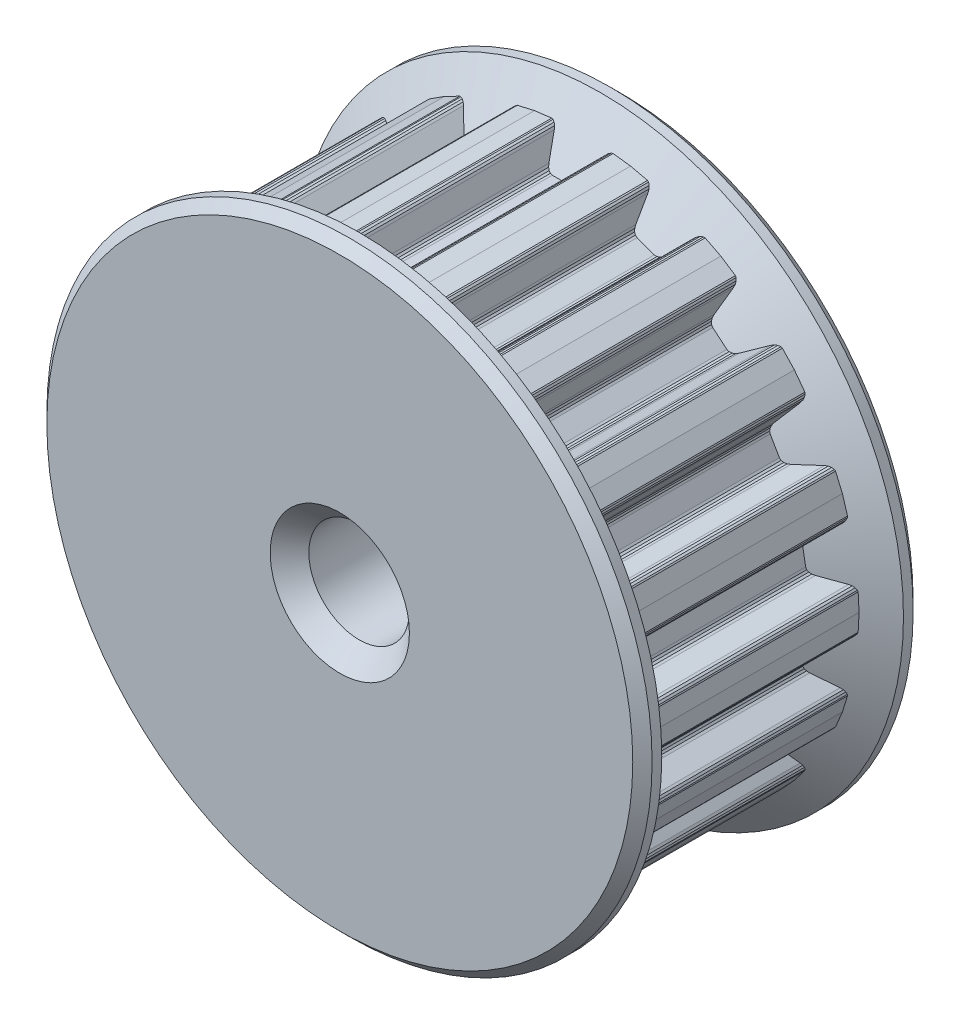
SolidWorks part; units mm, degrees
material "PLA"
ref_plane "Front Plane" through (0, 0, 0) normal (0, 0, 1) x (1, 0, 0)
ref_plane "Top Plane" through (0, 0, 0) normal (0, 1, 0) x (1, 0, 0)
ref_plane "Right Plane" through (0, 0, 0) normal (1, 0, 0) x (0, 0, -1)
sketch "Sketch1" plane through (0, 0, 0) normal (0, 0, 1) x (1, 0, 0)
  circle A0 centre (0, 0) radius 2.6
  circle A1 centre (0, 0) radius 12.65
  dimension "D1" = 5.2
  dimension "D2" = 25.3
extrude "Boss-Extrude1" add sketch "Sketch1" along normal mid plane 12.5
sketch "Sketch2" plane through (0, 0, 6.25) normal (0, 0, 1) x (1, 0, 0)
  circle A5 centre (0, 0) radius 2.6 construction
  circle A6 centre (0, 0) radius 2.6
  circle A8 centre (0, 0) radius 15.65
  circle A9 centre (0, 0) radius 15.65
  dimension "D1" = 3
extrude "Boss-Extrude2" add sketch "Sketch2" along normal blind 1
mirror "Mirror1" about plane through (0, 0, 0) normal (0, 0, 1) of "Boss-Extrude2"
chamfer "Chamfer1" distance 3 angle 35 2 edges at (12.65, 0, 6.25) (12.65, 0, -6.25) first distance on face at (12.65, 0, 6.25) first distance on face at (12.65, 0, -6.25)
chamfer "Chamfer2" distance 0.5 angle 45 2 edges at (15.65, 0, 7.25) (15.65, 0, -7.25)
chamfer "Chamfer3" distance 1 angle 45 2 edges at (2.6, 0, -7.25) (2.6, 0, 7.25)
sketch "Sketch3" plane through (0, 0, 0) normal (0, 0, 1) x (1, 0, 0)
  line L0 (-1.5107, -14.1885) -> (-1.4073, -14.1374)
  line L1 (-1.4073, -14.1374) -> (-1.3209, -14.0571)
  line L2 (-1.3209, -14.0571) -> (-1.2574, -13.9516)
  line L3 (-1.2574, -13.9516) -> (-0.845, -12.9908)
  line L4 (-0.845, -12.9908) -> (-0.7816, -12.8857)
  line L5 (-0.7816, -12.8857) -> (-0.6953, -12.8054)
  line L6 (-0.6953, -12.8054) -> (-0.5918, -12.7541)
  line L7 (-0.5918, -12.7541) -> (-0.477, -12.736)
  line L8 (-0.477, -12.736) -> (0.477, -12.736)
  line L9 (0.477, -12.736) -> (0.5918, -12.7541)
  line L10 (0.5918, -12.7541) -> (0.6953, -12.8054)
  line L11 (0.6953, -12.8054) -> (0.7816, -12.8857)
  line L12 (0.7816, -12.8857) -> (0.845, -12.9908)
  line L13 (0.845, -12.9908) -> (1.2574, -13.9516)
  line L14 (1.2574, -13.9516) -> (1.321, -14.0571)
  line L15 (1.321, -14.0571) -> (1.4074, -14.1374)
  line L16 (1.4074, -14.1374) -> (1.5109, -14.1885)
  line L17 (1.5109, -14.1885) -> (1.585, -14.2001)
  line L18 (1.585, -14.2001) -> (2.483, -14.0819)
  line L19 (2.483, -14.0819) -> (3.3673, -13.8858)
  line L20 (3.3673, -13.8858) -> (3.4332, -13.8495)
  line L21 (3.4332, -13.8495) -> (3.5129, -13.7661)
  line L22 (3.5129, -13.7661) -> (3.5665, -13.6611)
  line L23 (3.5665, -13.6611) -> (3.5902, -13.5403)
  line L24 (3.5902, -13.5403) -> (3.6491, -12.4964)
  line L25 (3.6491, -12.4964) -> (3.6727, -12.376)
  line L26 (3.6727, -12.376) -> (3.7264, -12.2709)
  line L27 (3.7264, -12.2709) -> (3.8061, -12.1873)
  line L28 (3.8061, -12.1873) -> (3.9077, -12.1311)
  line L29 (3.9077, -12.1311) -> (4.8042, -11.8048)
  line L30 (4.8042, -11.8048) -> (4.9182, -11.7825)
  line L31 (4.9182, -11.7825) -> (5.033, -11.7953)
  line L32 (5.033, -11.7953) -> (5.1417, -11.8413)
  line L33 (5.1417, -11.8413) -> (5.2372, -11.9184)
  line L34 (5.2372, -11.9184) -> (5.9533, -12.6802)
  line L35 (5.9533, -12.6802) -> (6.0491, -12.7575)
  line L36 (6.0491, -12.7575) -> (6.1578, -12.8034)
  line L37 (6.1578, -12.8034) -> (6.2725, -12.8161)
  line L38 (6.2725, -12.8161) -> (6.3461, -12.8016)
  line L39 (6.3461, -12.8016) -> (7.1496, -12.3834)
  line L40 (7.1496, -12.3834) -> (7.9135, -11.8967)
  line L41 (7.9135, -11.8967) -> (7.9629, -11.8401)
  line L42 (7.9629, -11.8401) -> (8.0093, -11.7344)
  line L43 (8.0093, -11.7344) -> (8.0238, -11.6174)
  line L44 (8.0238, -11.6174) -> (8.0047, -11.4958)
  line L45 (8.0047, -11.4958) -> (7.703, -10.4947)
  line L46 (7.703, -10.4947) -> (7.684, -10.3735)
  line L47 (7.684, -10.3735) -> (7.6985, -10.2564)
  line L48 (7.6985, -10.2564) -> (7.7448, -10.1506)
  line L49 (7.7448, -10.1506) -> (7.8212, -10.063)
  line L50 (7.8212, -10.063) -> (8.552, -9.4497)
  line L51 (8.552, -9.4497) -> (8.6515, -9.3898)
  line L52 (8.6515, -9.3898) -> (8.7637, -9.3626)
  line L53 (8.7637, -9.3626) -> (8.8816, -9.3686)
  line L54 (8.8816, -9.3686) -> (8.9977, -9.4084)
  line L55 (8.9977, -9.4084) -> (9.9312, -9.8793)
  line L56 (9.9312, -9.8793) -> (10.0476, -9.9192)
  line L57 (10.0476, -9.9192) -> (10.1655, -9.9252)
  line L58 (10.1655, -9.9252) -> (10.2776, -9.8979)
  line L59 (10.2776, -9.8979) -> (10.3418, -9.8591)
  line L60 (10.3418, -9.8591) -> (10.9538, -9.1913)
  line L61 (10.9538, -9.1913) -> (11.5052, -8.4727)
  line L62 (11.5052, -8.4727) -> (11.5323, -8.4025)
  line L63 (11.5323, -8.4025) -> (11.5397, -8.2874)
  line L64 (11.5397, -8.2874) -> (11.5133, -8.1725)
  line L65 (11.5133, -8.1725) -> (11.4538, -8.0647)
  line L66 (11.4538, -8.0647) -> (10.8279, -7.2272)
  line L67 (10.8279, -7.2272) -> (10.7685, -7.1198)
  line L68 (10.7685, -7.1198) -> (10.7422, -7.0048)
  line L69 (10.7422, -7.0048) -> (10.7495, -6.8895)
  line L70 (10.7495, -6.8895) -> (10.7912, -6.7811)
  line L71 (10.7912, -6.7811) -> (11.2682, -5.9549)
  line L72 (11.2682, -5.9549) -> (11.3412, -5.8646)
  line L73 (11.3412, -5.8646) -> (11.4374, -5.8006)
  line L74 (11.4374, -5.8006) -> (11.5502, -5.7659)
  line L75 (11.5502, -5.7659) -> (11.6729, -5.7636)
  line L76 (11.6729, -5.7636) -> (12.7112, -5.8869)
  line L77 (12.7112, -5.8869) -> (12.8343, -5.8845)
  line L78 (12.8343, -5.8845) -> (12.947, -5.8498)
  line L79 (12.947, -5.8498) -> (13.043, -5.7858)
  line L80 (13.043, -5.7858) -> (13.0902, -5.7274)
  line L81 (13.0902, -5.7274) -> (13.4368, -4.8906)
  line L82 (13.4368, -4.8906) -> (13.7092, -4.0267)
  line L83 (13.7092, -4.0267) -> (13.7106, -3.9515)
  line L84 (13.7106, -3.9515) -> (13.6782, -3.8408)
  line L85 (13.6782, -3.8408) -> (13.6142, -3.7418)
  line L86 (13.6142, -3.7418) -> (13.5213, -3.661)
  line L87 (13.5213, -3.661) -> (12.6467, -3.088)
  line L88 (12.6467, -3.088) -> (12.5542, -3.0074)
  line L89 (12.5542, -3.0074) -> (12.4901, -2.9083)
  line L90 (12.4901, -2.9083) -> (12.4576, -2.7975)
  line L91 (12.4576, -2.7975) -> (12.4597, -2.6814)
  line L92 (12.4597, -2.6814) -> (12.6254, -1.7418)
  line L93 (12.6254, -1.7418) -> (12.6631, -1.6319)
  line L94 (12.6631, -1.6319) -> (12.7316, -1.5389)
  line L95 (12.7316, -1.5389) -> (12.8257, -1.4678)
  line L96 (12.8257, -1.4678) -> (12.9402, -1.4237)
  line L97 (12.9402, -1.4237) -> (13.958, -1.1844)
  line L98 (13.958, -1.1844) -> (14.0729, -1.1401)
  line L99 (14.0729, -1.1401) -> (14.167, -1.0689)
  line L100 (14.167, -1.0689) -> (14.2353, -0.9759)
  line L101 (14.2353, -0.9759) -> (14.2596, -0.9049)
  line L102 (14.2596, -0.9049) -> (14.2991, 0)
  line L103 (14.2991, 0) -> (14.2596, 0.9049)
  line L104 (14.2596, 0.9049) -> (14.2353, 0.9761)
  line L105 (14.2353, 0.9761) -> (14.167, 1.069)
  line L106 (14.167, 1.069) -> (14.0729, 1.1401)
  line L107 (14.0729, 1.1401) -> (13.958, 1.1844)
  line L108 (13.958, 1.1844) -> (12.9402, 1.4237)
  line L109 (12.9402, 1.4237) -> (12.8257, 1.4678)
  line L110 (12.8257, 1.4678) -> (12.7316, 1.5389)
  line L111 (12.7316, 1.5389) -> (12.6631, 1.6319)
  line L112 (12.6631, 1.6319) -> (12.6254, 1.7418)
  line L113 (12.6254, 1.7418) -> (12.4597, 2.6814)
  line L114 (12.4597, 2.6814) -> (12.4576, 2.7975)
  line L115 (12.4576, 2.7975) -> (12.4901, 2.9083)
  line L116 (12.4901, 2.9083) -> (12.5542, 3.0074)
  line L117 (12.5542, 3.0074) -> (12.6467, 3.088)
  line L118 (12.6467, 3.088) -> (13.5213, 3.661)
  line L119 (13.5213, 3.661) -> (13.6141, 3.7419)
  line L120 (13.6141, 3.7419) -> (13.6782, 3.841)
  line L121 (13.6782, 3.841) -> (13.7106, 3.9517)
  line L122 (13.7106, 3.9517) -> (13.7091, 4.0267)
  line L123 (13.7091, 4.0267) -> (13.4368, 4.8906)
  line L124 (13.4368, 4.8906) -> (13.0901, 5.7274)
  line L125 (13.0901, 5.7274) -> (13.043, 5.7859)
  line L126 (13.043, 5.7859) -> (12.947, 5.8499)
  line L127 (12.947, 5.8499) -> (12.8342, 5.8846)
  line L128 (12.8342, 5.8846) -> (12.7112, 5.8869)
  line L129 (12.7112, 5.8869) -> (11.6729, 5.7636)
  line L130 (11.6729, 5.7636) -> (11.5502, 5.7659)
  line L131 (11.5502, 5.7659) -> (11.4374, 5.8006)
  line L132 (11.4374, 5.8006) -> (11.3412, 5.8646)
  line L133 (11.3412, 5.8646) -> (11.2682, 5.9549)
  line L134 (11.2682, 5.9549) -> (10.7912, 6.7811)
  line L135 (10.7912, 6.7811) -> (10.7495, 6.8895)
  line L136 (10.7495, 6.8895) -> (10.7422, 7.0048)
  line L137 (10.7422, 7.0048) -> (10.7685, 7.1198)
  line L138 (10.7685, 7.1198) -> (10.8279, 7.2272)
  line L139 (10.8279, 7.2272) -> (11.4538, 8.0647)
  line L140 (11.4538, 8.0647) -> (11.5133, 8.1725)
  line L141 (11.5133, 8.1725) -> (11.5396, 8.2875)
  line L142 (11.5396, 8.2875) -> (11.5322, 8.4027)
  line L143 (11.5322, 8.4027) -> (11.5051, 8.4727)
  line L144 (11.5051, 8.4727) -> (10.9538, 9.1913)
  line L145 (10.9538, 9.1913) -> (10.3418, 9.8591)
  line L146 (10.3418, 9.8591) -> (10.2775, 9.898)
  line L147 (10.2775, 9.898) -> (10.1654, 9.9253)
  line L148 (10.1654, 9.9253) -> (10.0476, 9.9193)
  line L149 (10.0476, 9.9193) -> (9.9312, 9.8793)
  line L150 (9.9312, 9.8793) -> (8.9977, 9.4084)
  line L151 (8.9977, 9.4084) -> (8.8816, 9.3686)
  line L152 (8.8816, 9.3686) -> (8.7637, 9.3626)
  line L153 (8.7637, 9.3626) -> (8.6515, 9.3898)
  line L154 (8.6515, 9.3898) -> (8.552, 9.4497)
  line L155 (8.552, 9.4497) -> (7.8212, 10.063)
  line L156 (7.8212, 10.063) -> (7.7448, 10.1506)
  line L157 (7.7448, 10.1506) -> (7.6985, 10.2564)
  line L158 (7.6985, 10.2564) -> (7.684, 10.3735)
  line L159 (7.684, 10.3735) -> (7.703, 10.4947)
  line L160 (7.703, 10.4947) -> (8.0047, 11.4958)
  line L161 (8.0047, 11.4958) -> (8.0238, 11.6174)
  line L162 (8.0238, 11.6174) -> (8.0092, 11.7345)
  line L163 (8.0092, 11.7345) -> (7.9628, 11.8402)
  line L164 (7.9628, 11.8402) -> (7.9135, 11.8967)
  line L165 (7.9135, 11.8967) -> (7.1496, 12.3834)
  line L166 (7.1496, 12.3834) -> (6.3461, 12.8016)
  line L167 (6.3461, 12.8016) -> (6.2723, 12.8161)
  line L168 (6.2723, 12.8161) -> (6.1577, 12.8035)
  line L169 (6.1577, 12.8035) -> (6.0491, 12.7576)
  line L170 (6.0491, 12.7576) -> (5.9533, 12.6802)
  line L171 (5.9533, 12.6802) -> (5.2372, 11.9184)
  line L172 (5.2372, 11.9184) -> (5.1417, 11.8413)
  line L173 (5.1417, 11.8413) -> (5.033, 11.7953)
  line L174 (5.033, 11.7953) -> (4.9182, 11.7825)
  line L175 (4.9182, 11.7825) -> (4.8042, 11.8048)
  line L176 (4.8042, 11.8048) -> (3.9077, 12.1311)
  line L177 (3.9077, 12.1311) -> (3.8061, 12.1873)
  line L178 (3.8061, 12.1873) -> (3.7264, 12.2709)
  line L179 (3.7264, 12.2709) -> (3.6727, 12.376)
  line L180 (3.6727, 12.376) -> (3.6491, 12.4964)
  line L181 (3.6491, 12.4964) -> (3.5902, 13.5403)
  line L182 (3.5902, 13.5403) -> (3.5665, 13.6611)
  line L183 (3.5665, 13.6611) -> (3.5127, 13.7661)
  line L184 (3.5127, 13.7661) -> (3.433, 13.8496)
  line L185 (3.433, 13.8496) -> (3.3673, 13.8858)
  line L186 (3.3673, 13.8858) -> (2.483, 14.0819)
  line L187 (2.483, 14.0819) -> (1.585, 14.2001)
  line L188 (1.585, 14.2001) -> (1.5107, 14.1885)
  line L189 (1.5107, 14.1885) -> (1.4073, 14.1374)
  line L190 (1.4073, 14.1374) -> (1.3209, 14.0571)
  line L191 (1.3209, 14.0571) -> (1.2574, 13.9516)
  line L192 (1.2574, 13.9516) -> (0.845, 12.9908)
  line L193 (0.845, 12.9908) -> (0.7816, 12.8857)
  line L194 (0.7816, 12.8857) -> (0.6953, 12.8054)
  line L195 (0.6953, 12.8054) -> (0.5918, 12.7541)
  line L196 (0.5918, 12.7541) -> (0.477, 12.736)
  line L197 (0.477, 12.736) -> (-0.477, 12.736)
  line L198 (-0.477, 12.736) -> (-0.5918, 12.7541)
  line L199 (-0.5918, 12.7541) -> (-0.6953, 12.8054)
  line L200 (-0.6953, 12.8054) -> (-0.7816, 12.8857)
  line L201 (-0.7816, 12.8857) -> (-0.845, 12.9908)
  line L202 (-0.845, 12.9908) -> (-1.2574, 13.9516)
  line L203 (-1.2574, 13.9516) -> (-1.321, 14.0571)
  line L204 (-1.321, 14.0571) -> (-1.4074, 14.1374)
  line L205 (-1.4074, 14.1374) -> (-1.5109, 14.1885)
  line L206 (-1.5109, 14.1885) -> (-1.585, 14.2001)
  line L207 (-1.585, 14.2001) -> (-2.483, 14.0819)
  line L208 (-2.483, 14.0819) -> (-3.3673, 13.8858)
  line L209 (-3.3673, 13.8858) -> (-3.4332, 13.8495)
  line L210 (-3.4332, 13.8495) -> (-3.5129, 13.7661)
  line L211 (-3.5129, 13.7661) -> (-3.5665, 13.6611)
  line L212 (-3.5665, 13.6611) -> (-3.5902, 13.5403)
  line L213 (-3.5902, 13.5403) -> (-3.6491, 12.4964)
  line L214 (-3.6491, 12.4964) -> (-3.6727, 12.376)
  line L215 (-3.6727, 12.376) -> (-3.7264, 12.2709)
  line L216 (-3.7264, 12.2709) -> (-3.8061, 12.1873)
  line L217 (-3.8061, 12.1873) -> (-3.9077, 12.1311)
  line L218 (-3.9077, 12.1311) -> (-4.8042, 11.8048)
  line L219 (-4.8042, 11.8048) -> (-4.9182, 11.7825)
  line L220 (-4.9182, 11.7825) -> (-5.033, 11.7953)
  line L221 (-5.033, 11.7953) -> (-5.1417, 11.8413)
  line L222 (-5.1417, 11.8413) -> (-5.2372, 11.9184)
  line L223 (-5.2372, 11.9184) -> (-5.9533, 12.6802)
  line L224 (-5.9533, 12.6802) -> (-6.0491, 12.7575)
  line L225 (-6.0491, 12.7575) -> (-6.1578, 12.8034)
  line L226 (-6.1578, 12.8034) -> (-6.2725, 12.8161)
  line L227 (-6.2725, 12.8161) -> (-6.3461, 12.8016)
  line L228 (-6.3461, 12.8016) -> (-7.1496, 12.3834)
  line L229 (-7.1496, 12.3834) -> (-7.9135, 11.8967)
  line L230 (-7.9135, 11.8967) -> (-7.9629, 11.8401)
  line L231 (-7.9629, 11.8401) -> (-8.0093, 11.7344)
  line L232 (-8.0093, 11.7344) -> (-8.0238, 11.6174)
  line L233 (-8.0238, 11.6174) -> (-8.0047, 11.4958)
  line L234 (-8.0047, 11.4958) -> (-7.703, 10.4947)
  line L235 (-7.703, 10.4947) -> (-7.684, 10.3735)
  line L236 (-7.684, 10.3735) -> (-7.6985, 10.2564)
  line L237 (-7.6985, 10.2564) -> (-7.7448, 10.1506)
  line L238 (-7.7448, 10.1506) -> (-7.8212, 10.063)
  line L239 (-7.8212, 10.063) -> (-8.552, 9.4497)
  line L240 (-8.552, 9.4497) -> (-8.6515, 9.3898)
  line L241 (-8.6515, 9.3898) -> (-8.7637, 9.3626)
  line L242 (-8.7637, 9.3626) -> (-8.8816, 9.3686)
  line L243 (-8.8816, 9.3686) -> (-8.9977, 9.4084)
  line L244 (-8.9977, 9.4084) -> (-9.9312, 9.8793)
  line L245 (-9.9312, 9.8793) -> (-10.0476, 9.9192)
  line L246 (-10.0476, 9.9192) -> (-10.1655, 9.9252)
  line L247 (-10.1655, 9.9252) -> (-10.2776, 9.8979)
  line L248 (-10.2776, 9.8979) -> (-10.3418, 9.8591)
  line L249 (-10.3418, 9.8591) -> (-10.9538, 9.1913)
  line L250 (-10.9538, 9.1913) -> (-11.5052, 8.4727)
  line L251 (-11.5052, 8.4727) -> (-11.5323, 8.4025)
  line L252 (-11.5323, 8.4025) -> (-11.5397, 8.2874)
  line L253 (-11.5397, 8.2874) -> (-11.5133, 8.1725)
  line L254 (-11.5133, 8.1725) -> (-11.4538, 8.0647)
  line L255 (-11.4538, 8.0647) -> (-10.8279, 7.2272)
  line L256 (-10.8279, 7.2272) -> (-10.7685, 7.1198)
  line L257 (-10.7685, 7.1198) -> (-10.7422, 7.0048)
  line L258 (-10.7422, 7.0048) -> (-10.7495, 6.8895)
  line L259 (-10.7495, 6.8895) -> (-10.7912, 6.7811)
  line L260 (-10.7912, 6.7811) -> (-11.2682, 5.9549)
  line L261 (-11.2682, 5.9549) -> (-11.3412, 5.8646)
  line L262 (-11.3412, 5.8646) -> (-11.4374, 5.8006)
  line L263 (-11.4374, 5.8006) -> (-11.5502, 5.7659)
  line L264 (-11.5502, 5.7659) -> (-11.6729, 5.7636)
  line L265 (-11.6729, 5.7636) -> (-12.7112, 5.8869)
  line L266 (-12.7112, 5.8869) -> (-12.8343, 5.8845)
  line L267 (-12.8343, 5.8845) -> (-12.947, 5.8498)
  line L268 (-12.947, 5.8498) -> (-13.043, 5.7858)
  line L269 (-13.043, 5.7858) -> (-13.0902, 5.7274)
  line L270 (-13.0902, 5.7274) -> (-13.4368, 4.8906)
  line L271 (-13.4368, 4.8906) -> (-13.7092, 4.0267)
  line L272 (-13.7092, 4.0267) -> (-13.7106, 3.9515)
  line L273 (-13.7106, 3.9515) -> (-13.6782, 3.8408)
  line L274 (-13.6782, 3.8408) -> (-13.6142, 3.7418)
  line L275 (-13.6142, 3.7418) -> (-13.5213, 3.661)
  line L276 (-13.5213, 3.661) -> (-12.6467, 3.088)
  line L277 (-12.6467, 3.088) -> (-12.5542, 3.0074)
  line L278 (-12.5542, 3.0074) -> (-12.4901, 2.9083)
  line L279 (-12.4901, 2.9083) -> (-12.4576, 2.7975)
  line L280 (-12.4576, 2.7975) -> (-12.4597, 2.6814)
  line L281 (-12.4597, 2.6814) -> (-12.6254, 1.7418)
  line L282 (-12.6254, 1.7418) -> (-12.6631, 1.6319)
  line L283 (-12.6631, 1.6319) -> (-12.7316, 1.5389)
  line L284 (-12.7316, 1.5389) -> (-12.8257, 1.4678)
  line L285 (-12.8257, 1.4678) -> (-12.9402, 1.4237)
  line L286 (-12.9402, 1.4237) -> (-13.958, 1.1844)
  line L287 (-13.958, 1.1844) -> (-14.0729, 1.1401)
  line L288 (-14.0729, 1.1401) -> (-14.167, 1.0689)
  line L289 (-14.167, 1.0689) -> (-14.2353, 0.9759)
  line L290 (-14.2353, 0.9759) -> (-14.2596, 0.9049)
  line L291 (-14.2596, 0.9049) -> (-14.2991, 0)
  line L292 (-14.2991, 0) -> (-14.2596, -0.9049)
  line L293 (-14.2596, -0.9049) -> (-14.2353, -0.9761)
  line L294 (-14.2353, -0.9761) -> (-14.167, -1.069)
  line L295 (-14.167, -1.069) -> (-14.0729, -1.1401)
  line L296 (-14.0729, -1.1401) -> (-13.958, -1.1844)
  line L297 (-13.958, -1.1844) -> (-12.9402, -1.4237)
  line L298 (-12.9402, -1.4237) -> (-12.8257, -1.4678)
  line L299 (-12.8257, -1.4678) -> (-12.7316, -1.5389)
  line L300 (-12.7316, -1.5389) -> (-12.6631, -1.6319)
  line L301 (-12.6631, -1.6319) -> (-12.6254, -1.7418)
  line L302 (-12.6254, -1.7418) -> (-12.4597, -2.6814)
  line L303 (-12.4597, -2.6814) -> (-12.4576, -2.7975)
  line L304 (-12.4576, -2.7975) -> (-12.4901, -2.9083)
  line L305 (-12.4901, -2.9083) -> (-12.5542, -3.0074)
  line L306 (-12.5542, -3.0074) -> (-12.6467, -3.088)
  line L307 (-12.6467, -3.088) -> (-13.5213, -3.661)
  line L308 (-13.5213, -3.661) -> (-13.6141, -3.7419)
  line L309 (-13.6141, -3.7419) -> (-13.6782, -3.841)
  line L310 (-13.6782, -3.841) -> (-13.7106, -3.9517)
  line L311 (-13.7106, -3.9517) -> (-13.7091, -4.0267)
  line L312 (-13.7091, -4.0267) -> (-13.4368, -4.8906)
  line L313 (-13.4368, -4.8906) -> (-13.0901, -5.7274)
  line L314 (-13.0901, -5.7274) -> (-13.043, -5.7859)
  line L315 (-13.043, -5.7859) -> (-12.947, -5.8499)
  line L316 (-12.947, -5.8499) -> (-12.8342, -5.8846)
  line L317 (-12.8342, -5.8846) -> (-12.7112, -5.8869)
  line L318 (-12.7112, -5.8869) -> (-11.6729, -5.7636)
  line L319 (-11.6729, -5.7636) -> (-11.5502, -5.7659)
  line L320 (-11.5502, -5.7659) -> (-11.4374, -5.8006)
  line L321 (-11.4374, -5.8006) -> (-11.3412, -5.8646)
  line L322 (-11.3412, -5.8646) -> (-11.2682, -5.9549)
  line L323 (-11.2682, -5.9549) -> (-10.7912, -6.7811)
  line L324 (-10.7912, -6.7811) -> (-10.7495, -6.8895)
  line L325 (-10.7495, -6.8895) -> (-10.7422, -7.0048)
  line L326 (-10.7422, -7.0048) -> (-10.7685, -7.1198)
  line L327 (-10.7685, -7.1198) -> (-10.8279, -7.2272)
  line L328 (-10.8279, -7.2272) -> (-11.4538, -8.0647)
  line L329 (-11.4538, -8.0647) -> (-11.5133, -8.1725)
  line L330 (-11.5133, -8.1725) -> (-11.5396, -8.2875)
  line L331 (-11.5396, -8.2875) -> (-11.5322, -8.4027)
  line L332 (-11.5322, -8.4027) -> (-11.5051, -8.4727)
  line L333 (-11.5051, -8.4727) -> (-10.9538, -9.1913)
  line L334 (-10.9538, -9.1913) -> (-10.3418, -9.8591)
  line L335 (-10.3418, -9.8591) -> (-10.2775, -9.898)
  line L336 (-10.2775, -9.898) -> (-10.1654, -9.9253)
  line L337 (-10.1654, -9.9253) -> (-10.0476, -9.9193)
  line L338 (-10.0476, -9.9193) -> (-9.9312, -9.8793)
  line L339 (-9.9312, -9.8793) -> (-8.9977, -9.4084)
  line L340 (-8.9977, -9.4084) -> (-8.8816, -9.3686)
  line L341 (-8.8816, -9.3686) -> (-8.7637, -9.3626)
  line L342 (-8.7637, -9.3626) -> (-8.6515, -9.3898)
  line L343 (-8.6515, -9.3898) -> (-8.552, -9.4497)
  line L344 (-8.552, -9.4497) -> (-7.8212, -10.063)
  line L345 (-7.8212, -10.063) -> (-7.7448, -10.1506)
  line L346 (-7.7448, -10.1506) -> (-7.6985, -10.2564)
  line L347 (-7.6985, -10.2564) -> (-7.684, -10.3735)
  line L348 (-7.684, -10.3735) -> (-7.703, -10.4947)
  line L349 (-7.703, -10.4947) -> (-8.0047, -11.4958)
  line L350 (-8.0047, -11.4958) -> (-8.0238, -11.6174)
  line L351 (-8.0238, -11.6174) -> (-8.0092, -11.7345)
  line L352 (-8.0092, -11.7345) -> (-7.9628, -11.8402)
  line L353 (-7.9628, -11.8402) -> (-7.9135, -11.8967)
  line L354 (-7.9135, -11.8967) -> (-7.1496, -12.3834)
  line L355 (-7.1496, -12.3834) -> (-6.3461, -12.8016)
  line L356 (-6.3461, -12.8016) -> (-6.2723, -12.8161)
  line L357 (-6.2723, -12.8161) -> (-6.1577, -12.8035)
  line L358 (-6.1577, -12.8035) -> (-6.0491, -12.7576)
  line L359 (-6.0491, -12.7576) -> (-5.9533, -12.6802)
  line L360 (-5.9533, -12.6802) -> (-5.2372, -11.9184)
  line L361 (-5.2372, -11.9184) -> (-5.1417, -11.8413)
  line L362 (-5.1417, -11.8413) -> (-5.033, -11.7953)
  line L363 (-5.033, -11.7953) -> (-4.9182, -11.7825)
  line L364 (-4.9182, -11.7825) -> (-4.8042, -11.8048)
  line L365 (-4.8042, -11.8048) -> (-3.9077, -12.1311)
  line L366 (-3.9077, -12.1311) -> (-3.8061, -12.1873)
  line L367 (-3.8061, -12.1873) -> (-3.7264, -12.2709)
  line L368 (-3.7264, -12.2709) -> (-3.6727, -12.376)
  line L369 (-3.6727, -12.376) -> (-3.6491, -12.4964)
  line L370 (-3.6491, -12.4964) -> (-3.5902, -13.5403)
  line L371 (-3.5902, -13.5403) -> (-3.5665, -13.6611)
  line L372 (-3.5665, -13.6611) -> (-3.5127, -13.7661)
  line L373 (-3.5127, -13.7661) -> (-3.433, -13.8496)
  line L374 (-3.433, -13.8496) -> (-3.3673, -13.8858)
  line L375 (-3.3673, -13.8858) -> (-2.483, -14.0819)
  line L376 (-2.483, -14.0819) -> (-1.585, -14.2001)
  line L377 (-1.585, -14.2001) -> (-1.5107, -14.1885)
  circle A0 centre (0, 0) radius 12.65 construction
  circle A1 centre (0, 0) radius 12.65
extrude "Boss-Extrude3" add sketch "Sketch3" along normal mid plane 12
sketch "Sketch4" plane through (0, 0, -7.25) normal (0, 0, -1) x (-1, 0, 0)
  line L1 (-3.25, -4) -> (3.25, -4)
  line L2 (-3.25, -4) -> (-3.25, -6.5)
  line L3 (-3.25, -6.5) -> (3.25, -6.5)
  line L4 (3.25, -4) -> (3.25, -6.5)
  line L5 (-3.25, -4) -> (3.25, -6.5) construction
  line L6 (-3.25, -6.5) -> (3.25, -4) construction
  point P0 (0, -5.25)
  dimension "D1" = 6.5
  dimension "D2" = 2.5
  dimension "D3" = 4
extrude "Cut-Extrude1" cut sketch "Sketch4" against normal blind 10.5
sketch "Sketch5" plane through (0, 0, 0) normal (0, 1, 0) x (1, 0, 0)
  circle A0 centre (0, 0) radius 2
  dimension "D1" = 4
extrude "Cut-Extrude2" cut sketch "Sketch5" against normal through all
ref_plane "Plane2" through (0, -20, 0) normal (0, 1, 0) x (1, 0, 0)
sketch "Sketch6" plane through (0, -20, 0) normal (0, 1, 0) x (1, 0, 0)
  circle A0 centre (0, 0) radius 3.25
  dimension "D1" = 6.5
extrude "Cut-Extrude3" cut sketch "Sketch6" along normal offset from surface (11.5 mm away) 2 up to face at (0, -6.5, -2)
